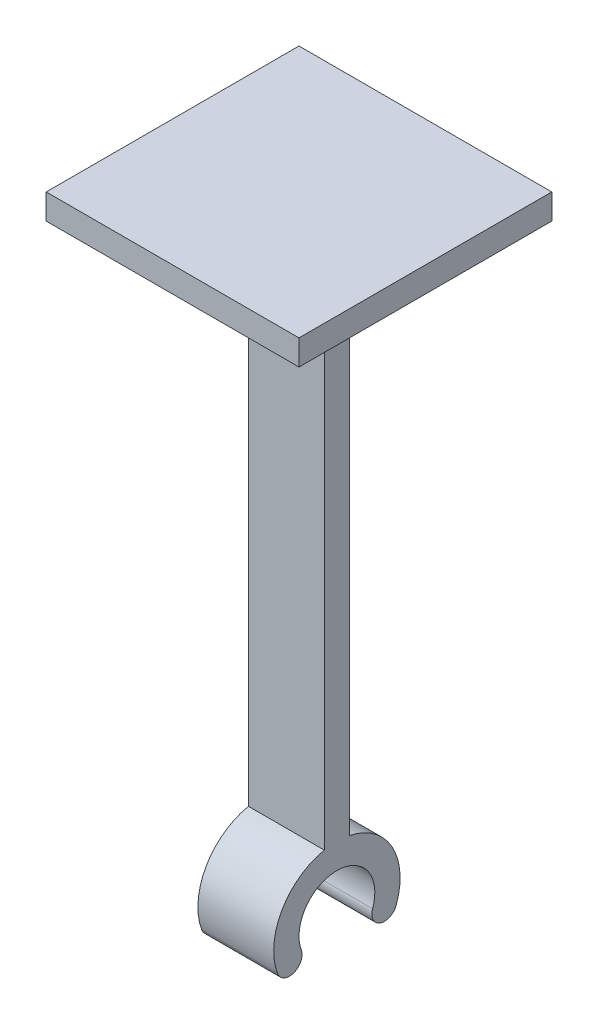
SolidWorks part; units mm, degrees
ref_plane "Front" through (0, 0, 0) normal (0, 0, 1) x (1, 0, 0)
ref_plane "Top" through (0, 0, 0) normal (0, 1, 0) x (1, 0, 0)
ref_plane "Right" through (0, 0, 0) normal (1, 0, 0) x (0, 0, -1)
sketch "Sketch1" plane through (0, 0, 0) normal (1, 0, 0) x (0, 0, -1)
  line L0 (0, 0) -> (-5, 0)
  line L1 (0, 0) -> (-4.6985, -1.7101)
  line L2 (0, 50) -> (0, -50) construction
  line L3 (0, 0) -> (4.6985, -1.7101)
  line L4 (-4.6985, -1.7101) -> (-3.7588, -1.3681)
  circle A0 centre (0, 0) radius 3
  circle A1 centre (0, 0) radius 5
  arc A2 (-4.6985, -1.7101) -> (-2.8191, -1.0261) centre (-3.7588, -1.3681) ccw
  arc A3 (4.6985, -1.7101) -> (2.8191, -1.0261) centre (3.7588, -1.3681) cw
  dimension "D1" = 20
  dimension "D3" = 10
  dimension "D4" = 6
  dimension "D2" = 1
extrude "Boss-Extrude1" add sketch "Sketch1" against normal blind 3 and the other way blind 3 contours L3 A1 L0 A0 | A3 L3 | L0 A1 L1 A0 | L1 A2 region at (0, -0.7055, 4.0009) region at (0, 0.1204, 4) region at (0, -1.7669, 3.6136) region at (0, -1.7669, -3.6136)
sketch "Sketch2" plane through (0, 0, 0) normal (1, 0, 0) x (0, 0, -1)
  line L0 (0, 0) -> (0, 5)
  line L1 (0, 5) -> (0, 3)
  line L2 (0, 3) -> (-1, 3)
  line L4 (-1, 3) -> (1, 3)
  line L5 (-1, 3) -> (-1, 46)
  line L6 (-1, 46) -> (1, 46)
  line L7 (1, 3) -> (1, 46)
  arc A0 (4.6985, -1.7101) -> (-4.6985, -1.7101) centre (0, 0) ccw construction
  dimension "D1" = 2
  dimension "D2" = 1
  dimension "D3" = 2
  dimension "D4" = 43
extrude "Boss-Extrude2" add sketch "Sketch2" along normal blind 3 contours L4 L7 L6 L5 L2 region at (0, 24.5, 0)
sketch "Sketch3" plane through (0, 0, 0) normal (1, 0, 0) x (0, 0, -1)
  line L0 (0, 46) -> (-1, 46)
  line L1 (-1, 46) -> (1, 46) construction
  line L3 (-1, 46) -> (1, 46)
  line L4 (-1, 46) -> (-1, 3)
  line L5 (-1, 3) -> (1, 3)
  line L6 (1, 46) -> (1, 3)
  dimension "D1" = 1
  dimension "D2" = 43
  dimension "2" = 2
extrude "Boss-Extrude3" add sketch "Sketch3" against normal blind 3 contours L6 L3 L0 L4 L5 region at (0, 24.5, 0)
sketch "Sketch4" plane through (0, 46, 0) normal (0, 1, 0) x (1, 0, 0)
  line L1 (-10, -10) -> (10, -10)
  line L2 (-10, -10) -> (-10, 10)
  line L3 (-10, 10) -> (10, 10)
  line L4 (10, -10) -> (10, 10)
  line L5 (0, 10) -> (0, -10) construction
  line L6 (-10, 0) -> (10, 0) construction
  point P1 (0, 0)
  dimension "D1" = 20
  dimension "D2" = 20
extrude "Boss-Extrude4" add sketch "Sketch4" along normal blind 2
